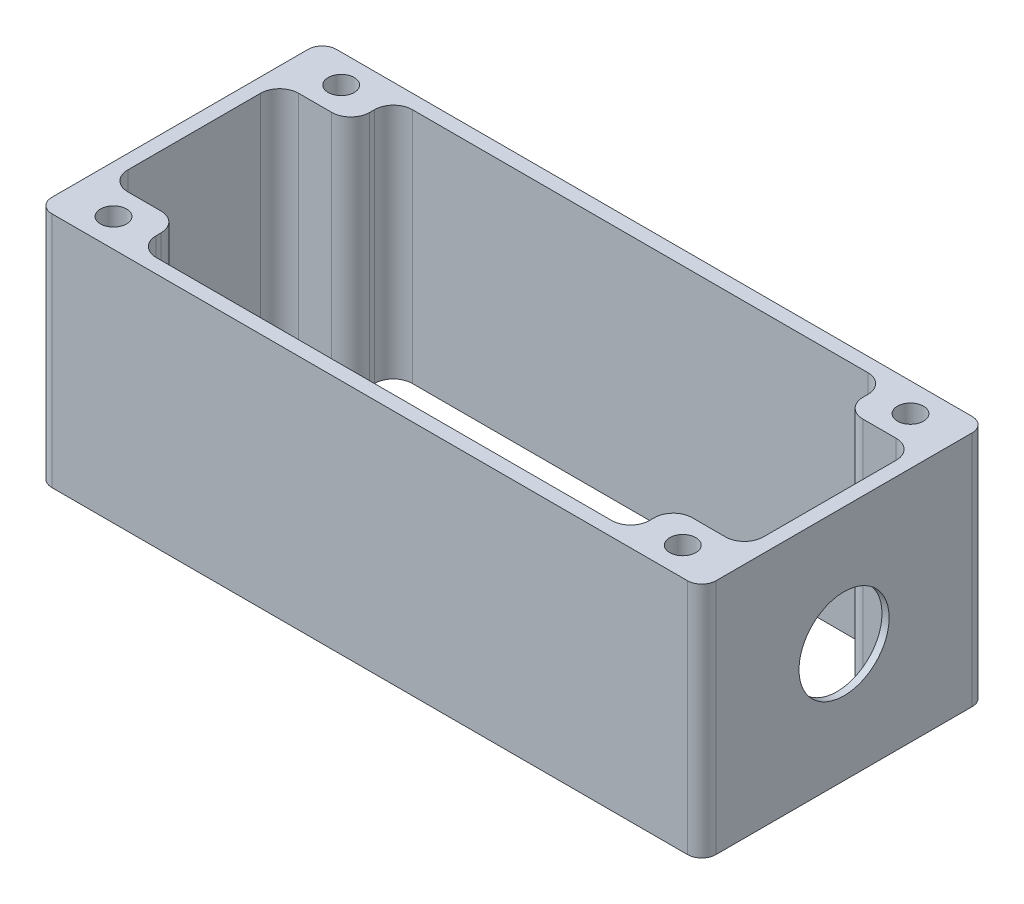
SolidWorks part; units mm, degrees
note: The reader was unsure of these and kept them because the rebuilt part matched: shared geometry of "Sketch1<2>".
ref_plane "Front Plane" through (0, 0, 0) normal (0, 0, 1) x (1, 0, 0)
ref_plane "Top Plane" through (0, 0, 0) normal (0, 1, 0) x (1, 0, 0)
ref_plane "Right Plane" through (0, 0, 0) normal (1, 0, 0) x (0, 0, -1)
sketch "Sketch1" plane through (0, 0, 0) normal (0, 1, 0) x (1, 0, 0)
  line L0 (65, -19) -> (65, 19) construction
  line L1 (-65, -19) -> (65, -19) construction
  line L2 (-65, 19) -> (-65, -19) construction
  line L3 (65, 19) -> (-65, 19) construction
  line L4 (67, 30) -> (-67, 30)
  line L5 (-70, 27) -> (-70, -27)
  line L6 (-67, -30) -> (67, -30)
  line L7 (70, -27) -> (70, 27)
  line L8 (67, 30) -> (-67, 30)
  line L9 (-70, 27) -> (-70, -27)
  line L10 (-67, -30) -> (67, -30)
  line L11 (70, -27) -> (70, 27)
  line L12 (65, -19) -> (65, 19)
  line L13 (-65, -19) -> (65, -19)
  line L14 (-65, 19) -> (-65, -19)
  line L15 (65, 19) -> (-65, 19)
  circle A0 centre (-60, 24) radius 2.75 construction
  circle A1 centre (-60, -24) radius 2.75 construction
  circle A2 centre (60, -24) radius 2.75 construction
  circle A3 centre (60, 24) radius 2.75 construction
  arc A4 (-67, 30) -> (-70, 27) centre (-67, 27) ccw
  arc A5 (-70, -27) -> (-67, -30) centre (-67, -27) ccw
  arc A6 (67, -30) -> (70, -27) centre (67, -27) ccw
  arc A7 (70, 27) -> (67, 30) centre (67, 27) ccw
  arc A8 (-67, 30) -> (-70, 27) centre (-67, 27) ccw
  arc A9 (-70, -27) -> (-67, -30) centre (-67, -27) ccw
  arc A10 (67, -30) -> (70, -27) centre (67, -27) ccw
  arc A11 (70, 27) -> (67, 30) centre (67, 27) ccw
  circle A12 centre (-60, 24) radius 2.75
  circle A13 centre (-60, -24) radius 2.75
  circle A14 centre (60, -24) radius 2.75
  circle A15 centre (60, 24) radius 2.75
  dimension "D1" = 0
extrude "Boss-Extrude1" add sketch "Sketch1" along normal blind 10
extrude "Boss-Extrude2" add sketch "Sketch1<2>" along normal blind 10
sketch "Sketch1<2>" plane through (0, 0, 0) normal (0, 1, 0) x (1, 0, 0) same geometry as "Sketch1"
sketch "Sketch14" plane through (0, 10, 0) normal (0, 1, 0) x (1, 0, 0)
  line L0 (67, 30) -> (-67, 30) construction
  line L1 (52, -27) -> (-52, -27)
  line L2 (52, -27) -> (52, 27)
  line L3 (52, 27) -> (-52, 27)
  line L4 (-52, -27) -> (-52, 27)
  line L5 (52, -27) -> (-52, 27) construction
  line L6 (52, 27) -> (-52, -27) construction
  line L7 (-67, 18) -> (67, 18)
  line L8 (-67, 18) -> (-67, -18)
  line L9 (-67, -18) -> (67, -18)
  line L10 (67, 18) -> (67, -18)
  line L11 (-67, 18) -> (67, -18) construction
  line L12 (-67, -18) -> (67, 18) construction
  line L13 (-70, 27) -> (-70, -27) construction
  line L14 (-67, -30) -> (67, -30) construction
  point P0 (0, 0)
  point P6 (0, 0)
  dimension "D1" = 3
  dimension "D2" = 3
  dimension "D3" = 12
  dimension "D4" = 18
extrude "Cut-Extrude2" cut sketch "Sketch14" against normal through all contours L8 L9 L4 L7 | L4 L9 L2 L7 | L4 L7 L2 L3 | L10 L7 L2 L9 | L9 L4 L1 L2
fillet "Fillet2" radius 4 12 edges at (52, 5, 27) (67, 5, 18) (52, 5, 18) (67, 5, -18) (52, 5, -18) (52, 5, -27) (-52, 5, 27) (-52, 5, 18) (-67, 5, 18) (-67, 5, -18) (-52, 5, -18) (-52, 5, -27)
sketch "Sketch15" plane through (0, 10, 0) normal (0, 1, 0) x (1, 0, 0)
  line L0 (67, 30) -> (-67, 30) construction
  line L1 (70, -27) -> (70, 27) construction
  line L2 (-67, -30) -> (67, -30) construction
  line L3 (-70, 27) -> (-70, -27) construction
  line L4 (67, 30) -> (-67, 30)
  line L5 (70, -27) -> (70, 27)
  line L6 (-67, -30) -> (67, -30)
  line L7 (-70, 27) -> (-70, -27)
  line L12 (56, -18) -> (63, -18)
  line L13 (52, -23) -> (52, -22)
  line L14 (-48, -27) -> (48, -27)
  line L15 (-52, -22) -> (-52, -23)
  line L16 (-63, -18) -> (-56, -18)
  line L17 (-67, 14) -> (-67, -14)
  line L18 (-56, 18) -> (-63, 18)
  line L19 (-52, 23) -> (-52, 22)
  line L20 (48, 27) -> (-48, 27)
  line L21 (52, 22) -> (52, 23)
  line L22 (63, 18) -> (56, 18)
  line L23 (67, -14) -> (67, 14)
  line L24 (56, -18) -> (63, -18)
  line L25 (52, -23) -> (52, -22)
  line L26 (-48, -27) -> (48, -27)
  line L27 (-52, -22) -> (-52, -23)
  line L28 (-63, -18) -> (-56, -18)
  line L29 (-67, 14) -> (-67, -14)
  line L30 (-56, 18) -> (-63, 18)
  line L31 (-52, 23) -> (-52, 22)
  line L32 (48, 27) -> (-48, 27)
  line L33 (52, 22) -> (52, 23)
  line L34 (63, 18) -> (56, 18)
  line L35 (67, -14) -> (67, 14)
  arc A0 (70, 27) -> (67, 30) centre (67, 27) ccw construction
  circle A1 centre (-60, 24) radius 2.75
  circle A2 centre (-60, 24) radius 2.75
  circle A3 centre (-60, -24) radius 2.75
  circle A4 centre (-60, -24) radius 2.75
  circle A5 centre (60, -24) radius 2.75
  circle A6 centre (60, -24) radius 2.75
  circle A7 centre (60, 24) radius 2.75
  circle A8 centre (60, 24) radius 2.75
  arc A9 (67, -30) -> (70, -27) centre (67, -27) ccw construction
  arc A10 (-70, -27) -> (-67, -30) centre (-67, -27) ccw construction
  arc A11 (-67, 30) -> (-70, 27) centre (-67, 27) ccw construction
  arc A12 (70, 27) -> (67, 30) centre (67, 27) ccw
  arc A13 (67, -30) -> (70, -27) centre (67, -27) ccw
  arc A14 (-70, -27) -> (-67, -30) centre (-67, -27) ccw
  arc A15 (-67, 30) -> (-70, 27) centre (-67, 27) ccw
  arc A20 (56, -18) -> (52, -22) centre (56, -22) ccw
  arc A21 (48, -27) -> (52, -23) centre (48, -23) ccw
  arc A22 (-52, -23) -> (-48, -27) centre (-48, -23) ccw
  arc A23 (-52, -22) -> (-56, -18) centre (-56, -22) ccw
  arc A24 (-67, -14) -> (-63, -18) centre (-63, -14) ccw
  arc A25 (-63, 18) -> (-67, 14) centre (-63, 14) ccw
  arc A26 (-56, 18) -> (-52, 22) centre (-56, 22) ccw
  arc A27 (-48, 27) -> (-52, 23) centre (-48, 23) ccw
  arc A28 (52, 23) -> (48, 27) centre (48, 23) ccw
  arc A29 (52, 22) -> (56, 18) centre (56, 22) ccw
  arc A30 (67, 14) -> (63, 18) centre (63, 14) ccw
  arc A31 (63, -18) -> (67, -14) centre (63, -14) ccw
  arc A32 (56, -18) -> (52, -22) centre (56, -22) ccw
  arc A33 (48, -27) -> (52, -23) centre (48, -23) ccw
  arc A34 (-52, -23) -> (-48, -27) centre (-48, -23) ccw
  arc A35 (-52, -22) -> (-56, -18) centre (-56, -22) ccw
  arc A36 (-67, -14) -> (-63, -18) centre (-63, -14) ccw
  arc A37 (-63, 18) -> (-67, 14) centre (-63, 14) ccw
  arc A38 (-56, 18) -> (-52, 22) centre (-56, 22) ccw
  arc A39 (-48, 27) -> (-52, 23) centre (-48, 23) ccw
  arc A40 (52, 23) -> (48, 27) centre (48, 23) ccw
  arc A41 (52, 22) -> (56, 18) centre (56, 22) ccw
  arc A42 (67, 14) -> (63, 18) centre (63, 14) ccw
  arc A43 (63, -18) -> (67, -14) centre (63, -14) ccw
  dimension "D1" = 0
  dimension "D2" = 0
  dimension "D3" = 0
  dimension "D4" = 0
  dimension "D5" = 0
extrude "Boss-Extrude3" add sketch "Sketch15" along normal blind 40
sketch "Sketch16" plane through (70, 0, 0) normal (1, 0, 0) x (0, 0, -1)
  line L0 (-27, 0) -> (27, 0) construction
  circle A0 centre (0, 25) radius 9.5
  point P4 (0, 0)
  point P5 (0, 0)
  dimension "D1" = 19
  dimension "D2" = 25
extrude "Cut-Extrude3" cut sketch "Sketch16" against normal up to next
sketch "Sketch17" plane through (67, 0, 0) normal (-1, 0, 0) x (0, 0, 1)
  circle A2 centre (0, 25) radius 13.5
  circle A3 centre (0, 25) radius 13.5
  dimension "D1" = 4
extrude "Cut-Extrude4" cut sketch "Sketch17" against normal blind 1.5
